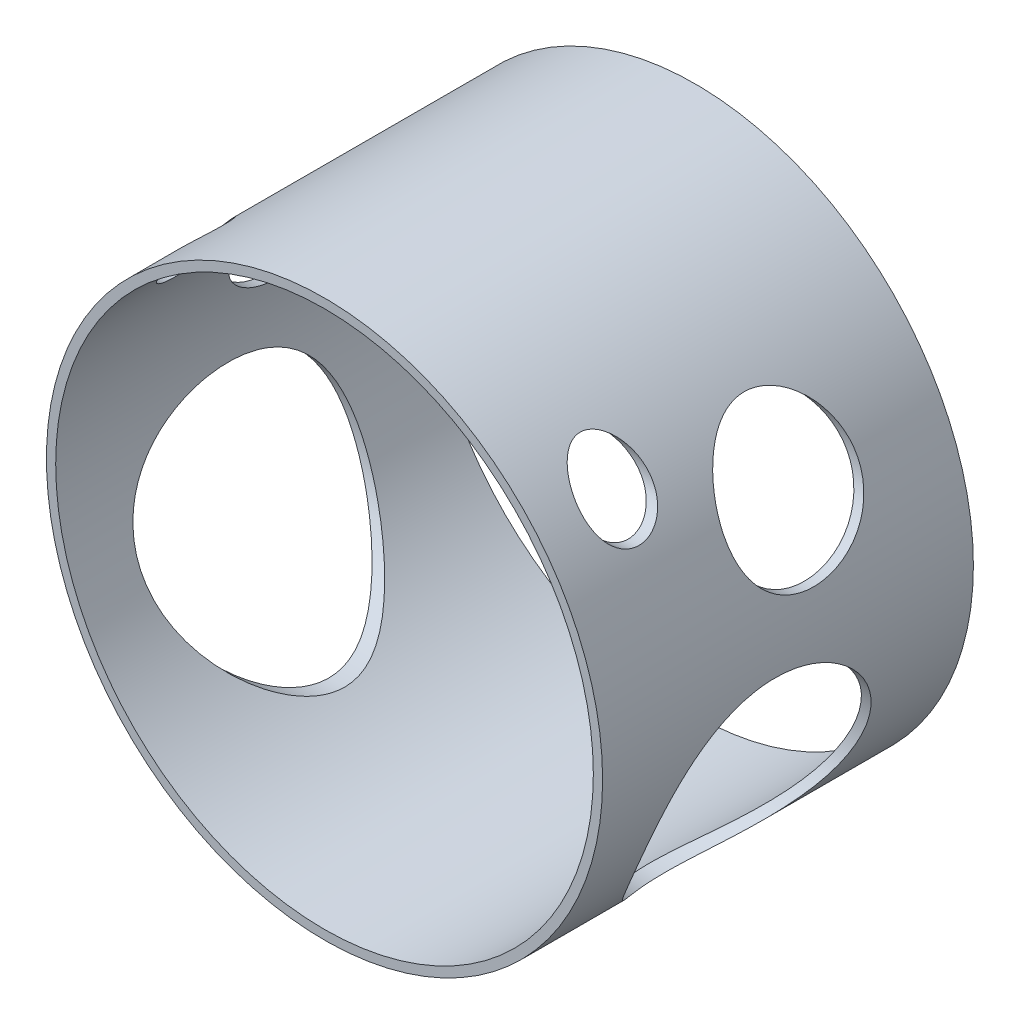
SolidWorks part; units mm, degrees
ref_plane "Front Plane" through (0, 0, 0) normal (0, 0, 1) x (1, 0, 0)
ref_plane "Top Plane" through (0, 0, 0) normal (0, 1, 0) x (1, 0, 0)
ref_plane "Right Plane" through (0, 0, 0) normal (1, 0, 0) x (0, 0, -1)
sketch "Sketch2" plane through (0, 0, 0) normal (0, 0, 1) x (1, 0, 0)
  circle A0 centre (0, 1.1498) radius 43.5
  circle A2 centre (0, 1.1498) radius 45
  dimension "D1" = 87
  dimension "D2" = 90
extrude "Boss-Extrude2" add sketch "Sketch2" along normal blind 60
sketch "Sketch15" plane through (0, 0, 0) normal (1, 0, 0) x (0, 0, -1)
  circle A0 centre (-32.0643, 24.1701) radius 18.1518
  circle A1 centre (-32.0643, -16.6159) radius 18.0662
extrude "Cut-Extrude2" cut sketch "Sketch15" against normal blind 50 and the other way blind 50 contours A1
sketch "Sketch16" plane through (0, 0, 0) normal (1, 0, 0) x (0, 0, -1)
  circle A0 centre (-47.578, 30.0503) radius 5.5558
  circle A1 centre (-24.933, 21.0423) radius 10.8623
  point P4 (0, 0)
extrude "Cut-Extrude3" cut sketch "Sketch16" against normal blind 50 and the other way blind 50
